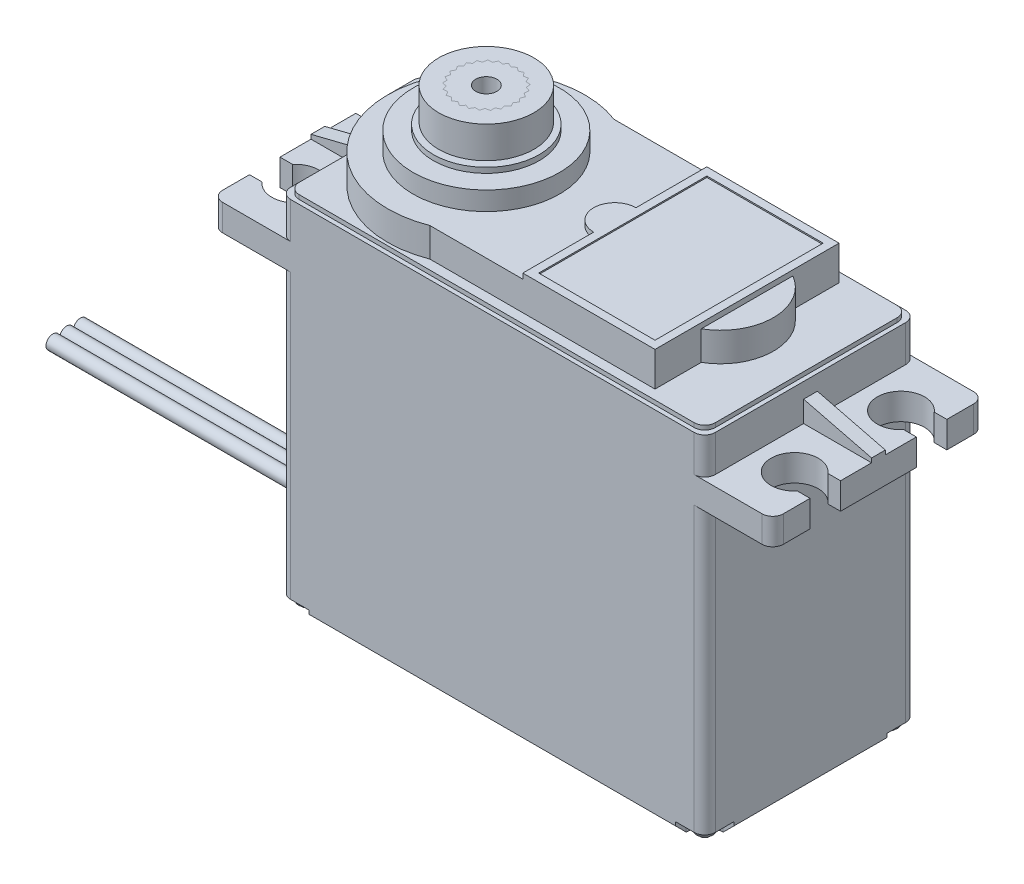
SolidWorks part; units mm, degrees
other "Camera1"
ref_plane "Front Plane" through (0, 0, 0) normal (0, 0, 1) x (1, 0, 0)
ref_plane "Top Plane" through (0, 0, 0) normal (0, 1, 0) x (1, 0, 0)
ref_plane "Right Plane" through (0, 0, 0) normal (1, 0, 0) x (0, 0, -1)
sketch "Sketch1" plane through (0, 0, 0) normal (0, 1, 0) x (1, 0, 0)
  line L1 (20.075, -10) -> (-20.075, -10)
  line L2 (20.075, -10) -> (20.075, 10)
  line L3 (20.075, 10) -> (-20.075, 10)
  line L4 (-20.075, -10) -> (-20.075, 10)
  line L5 (20.075, -10) -> (-20.075, 10) construction
  line L6 (20.075, 10) -> (-20.075, -10) construction
  point P0 (0, 0)
  dimension "D1" = 20
  dimension "D2" = 40.15
extrude "Boss-Extrude1" add sketch "Sketch1" along normal blind 34.5
sketch "Sketch2" plane through (0, 34.5, 0) normal (0, 1, 0) x (1, 0, 0)
  line L0 (-20.075, 0) -> (20.075, 0) construction
  line L1 (-20.075, 10) -> (-20.075, -10) construction
  line L2 (20.075, -10) -> (20.075, 10) construction
  line L3 (14.075, -4.3301) -> (14.075, -8.7)
  line L4 (-7.2047, 8.7) -> (14.075, 8.7)
  line L6 (-7.2047, -8.7) -> (14.075, -8.7)
  line L7 (14.075, 8.7) -> (14.075, 4.3301)
  arc A0 (-7.2047, 8.7) -> (-7.2047, -8.7) centre (-10.575, 0) ccw
  arc A1 (14.075, -4.3301) -> (14.075, 4.3301) centre (11.575, 0) ccw
  dimension "D2" = 18.66
  dimension "D5" = 10
  dimension "D1" = 9.5
  dimension "D3" = 17.4
  dimension "D4" = 6
  dimension "D6" = 8.5
sketch "Sketch3" plane through (0, 34.5, 0) normal (0, 1, 0) x (1, 0, 0)
  line L8 (-19.675, 9.6) -> (-19.675, -9.6)
  line L9 (-19.675, -9.6) -> (19.675, -9.6)
  line L10 (19.675, -9.6) -> (19.675, 9.6)
  line L11 (19.675, 9.6) -> (-19.675, 9.6)
  line L12 (-19.675, 9.6) -> (-19.675, -9.6)
  line L13 (-19.675, -9.6) -> (19.675, -9.6)
  line L14 (19.675, -9.6) -> (19.675, 9.6)
  line L15 (19.675, 9.6) -> (-19.675, 9.6)
  line L16 (-20.075, 10) -> (-20.075, -10)
  line L17 (-20.075, -10) -> (20.075, -10)
  line L18 (20.075, -10) -> (20.075, 10)
  line L19 (20.075, 10) -> (-20.075, 10)
  line L20 (-20.075, 10) -> (-20.075, -10)
  line L21 (-20.075, -10) -> (20.075, -10)
  line L22 (20.075, -10) -> (20.075, 10)
  line L23 (20.075, 10) -> (-20.075, 10)
  dimension "D1" = 0.4
  dimension "D2" = 0
extrude "Cut-Extrude1" cut sketch "Sketch3" against normal blind 0.4
extrude "Boss-Extrude2" add sketch "Sketch2" along normal mid plane 5.5
sketch "Sketch4" plane through (0, 37.25, 0) normal (0, 1, 0) x (1, 0, 0)
  circle A0 centre (-10.575, 0) radius 6.925
  dimension "D1" = 13.85
extrude "Boss-Extrude3" add sketch "Sketch4" along normal blind 1.77
sketch "Sketch5" plane through (0, 39.02, 0) normal (0, 1, 0) x (1, 0, 0)
  circle A0 centre (-10.575, 0) radius 5
  dimension "D1" = 10
extrude "Boss-Extrude4" add sketch "Sketch5" along normal blind 0.5
sketch "Sketch6" plane through (0, 37.25, 0) normal (0, 1, 0) x (1, 0, 0)
  line L0 (-7.2047, -8.7) -> (14.075, -8.7) construction
  line L1 (14.075, 8.7) -> (1.575, 8.7)
  line L2 (14.075, 8.7) -> (14.075, -8.7)
  line L3 (14.075, -8.7) -> (1.575, -8.7)
  line L4 (1.575, 8.7) -> (1.575, 2)
  line L5 (2.325, 7.95) -> (2.325, -7.95)
  line L6 (13.325, -7.95) -> (2.325, -7.95)
  line L7 (13.325, 7.95) -> (13.325, -7.95)
  line L8 (13.325, 7.95) -> (2.325, 7.95)
  line L9 (14.075, 0) -> (0, 0) construction
  line L10 (1.575, -2) -> (1.575, -8.7)
  line L11 (1.575, 8.7) -> (1.575, -8.7) construction
  line L12 (14.075, -8.7) -> (14.075, -4.3301) construction
  arc A0 (1.575, 2) -> (1.575, -2) centre (1.575, 0) ccw
  dimension "D3" = 4
  dimension "D2" = 12.5
  dimension "D1" = 0.75
extrude "Boss-Extrude5" add sketch "Sketch6" along normal blind 0.5
sketch "Sketch7" plane through (0, 37.25, 0) normal (0, 1, 0) x (1, 0, 0)
  line L4 (13.325, 7.95) -> (2.325, 7.95)
  line L5 (2.325, 7.95) -> (2.325, -7.95)
  line L6 (2.325, -7.95) -> (13.325, -7.95)
  line L7 (13.325, -7.95) -> (13.325, 7.95)
  line L8 (13.325, 7.95) -> (2.325, 7.95)
  line L9 (2.325, 7.95) -> (2.325, -7.95)
  line L10 (2.325, -7.95) -> (13.325, -7.95)
  line L11 (13.325, -7.95) -> (13.325, 7.95)
  dimension "D1" = 0
extrude "Boss-Extrude6" add sketch "Sketch7" along normal offset from surface (0.375 mm away) 0.125 up to face at (5.4083, 37.75, 0)
fillet "Fillet1" radius 1 8 edges at (19.675, 34.3, -9.6) (-19.675, 34.3, -9.6) (-19.675, 34.3, 9.6) (19.675, 34.3, 9.6) (20.075, 17.05, -10) (20.075, 17.05, 10) (-20.075, 17.05, -10) (-20.075, 17.05, 10)
sketch "Sketch10" plane through (0, 0, 0) normal (0, 1, 0) x (1, 0, 0)
  line L0 (-19.075, 10) -> (-25.5, 10)
  line L1 (-19.075, -10) -> (-25.5, -10)
  line L2 (-26.5, -9) -> (-26.5, -6.465)
  line L3 (19.075, 10) -> (25.5, 10)
  line L4 (26.5, 9) -> (26.5, 6.465)
  line L5 (25.5, -10) -> (19.075, -10)
  line L6 (23.6, 10) -> (23.6, -10) construction
  line L7 (-23.6, 10) -> (-23.6, -10) construction
  line L8 (-26.5, 0) -> (26.5, 0) construction
  line L9 (0, 10) -> (0, -10) construction
  line L10 (19.075, 10) -> (-19.075, 10) construction
  line L11 (-19.075, -10) -> (19.075, -10) construction
  line L12 (-23.6, 5.025) -> (23.6, 5.025) construction
  line L13 (23.6, -5.025) -> (-23.6, -5.025) construction
  line L14 (-26.5, 6.465) -> (-26.5, 9)
  line L15 (-26.5, 6.465) -> (-25.3093, 6.465)
  line L16 (-26.5, -3.585) -> (-26.5, 3.585)
  line L17 (-26.5, 3.585) -> (-25.3093, 3.585)
  line L18 (26.5, 3.585) -> (26.5, -3.585)
  line L19 (-26.5, -3.585) -> (-25.3093, -3.585)
  line L20 (26.5, -6.465) -> (26.5, -9)
  line L21 (-26.5, -6.465) -> (-25.3093, -6.465)
  line L22 (19.075, 10) -> (19.075, -10)
  line L23 (26.5, 6.465) -> (25.3093, 6.465)
  line L24 (-19.075, 10) -> (-19.075, -10)
  line L25 (26.5, 3.585) -> (25.3093, 3.585)
  line L27 (26.5, -3.585) -> (25.3093, -3.585)
  line L29 (26.5, -6.465) -> (25.3093, -6.465)
  arc A0 (-25.3093, 3.585) -> (-25.3093, 6.465) centre (-23.6, 5.025) ccw
  arc A1 (-25.3093, -6.465) -> (-25.3093, -3.585) centre (-23.6, -5.025) ccw
  arc A2 (25.3093, 6.465) -> (25.3093, 3.585) centre (23.6, 5.025) ccw
  arc A3 (25.3093, -3.585) -> (25.3093, -6.465) centre (23.6, -5.025) ccw
  arc A4 (-25.5, -10) -> (-26.5, -9) centre (-25.5, -9) cw
  arc A5 (-25.5, 10) -> (-26.5, 9) centre (-25.5, 9) ccw
  arc A6 (26.5, -9) -> (25.5, -10) centre (25.5, -9) cw
  arc A7 (25.5, 10) -> (26.5, 9) centre (25.5, 9) cw
  dimension "D1" = 4.47
  dimension "D5" = 1
  dimension "D2" = 10.05
  dimension "D3" = 47.2
  dimension "D4" = 53
  dimension "D6" = 2.88
  dimension "D7" = 2.88
  dimension "D8" = 2.88
  dimension "D9" = 2.88
extrude "Boss-Extrude7" add sketch "Sketch10" along normal blind 2.5 from offset 28.15
sketch "Sketch11" plane through (0, 0, 0) normal (0, 0, 1) x (1, 0, 0)
  line L0 (-20.075, 32.65) -> (-26.5, 31.0484)
  line L1 (-20.075, 30.65) -> (-20.075, 34.1) construction
  line L2 (-20.075, 32.65) -> (-20.075, 30.65)
  line L3 (-20.075, 30.65) -> (-26.5, 30.65)
  line L4 (20.075, 32.65) -> (26.5, 31.0484)
  line L5 (20.075, 34.1) -> (20.075, 30.65) construction
  line L6 (20.075, 32.65) -> (20.075, 30.65)
  line L7 (20.075, 30.65) -> (26.5, 30.65)
  line L8 (-26.5, 31.0484) -> (-26.5, 30.65)
  line L9 (26.5, 31.0484) -> (26.5, 30.65)
  dimension "D1" = 2
  dimension "D2" = 2
  dimension "D3" = 0.3984
extrude "Boss-Extrude8" add sketch "Sketch11" along normal mid plane 1.3
sketch "Sketch12" plane through (0, 0, 0) normal (0, -1, 0) x (1, 0, 0)
  line L0 (19.7821, 9.7071) -> (19.075, 9) construction
  line L2 (17.325, 9) -> (17.325, 10)
  line L4 (-19.075, 10) -> (19.075, 10) construction
  line L5 (19.075, 7.25) -> (20.075, 7.25)
  line L6 (20.075, -9) -> (20.075, 9) construction
  line L7 (17.325, 10) -> (19.075, 10)
  line L8 (20.075, 9) -> (20.075, 7.25)
  arc A1 (17.325, 9) -> (19.075, 7.25) centre (19.075, 9) ccw
  arc A2 (20.075, 9) -> (19.075, 10) centre (19.075, 9) ccw construction
  arc A3 (20.075, 9) -> (19.075, 10) centre (19.075, 9) ccw construction
  arc A4 (20.075, 9) -> (19.075, 10) centre (19.075, 9) ccw
  point P0 (19.075, 9)
  dimension "D1" = 3.5
extrude "Cut-Extrude2" cut sketch "Sketch12" against normal blind 1.35
mirror "Mirror1" about plane through (0, 0, 0) normal (0, 0, 1) of "Cut-Extrude2"
mirror "Mirror2" about plane through (0, 0, 0) normal (1, 0, 0) of "Mirror1"
chamfer "Chamfer1" distance 1 angle 45 4 edges at (20.075, 0, 0) (0, 0, -10) (-20.075, 0, 0) (0, 0, 10)
sketch "Sketch13" plane through (0, 39.52, 0) normal (0, 1, 0) x (1, 0, 0)
  line L0 (-10.575, 2.935) -> (-10.9115, 2.6638)
  line L1 (-10.575, 2.935) -> (-10.2385, 2.6638)
  line L2 (-10.575, 2.935) -> (-10.575, 0) construction
  line L3 (-9.8451, 2.8428) -> (-9.5866, 2.4964)
  line L4 (-9.8451, 2.8428) -> (-10.2385, 2.6638)
  line L5 (-9.1611, 2.572) -> (-8.9968, 2.1722)
  line L6 (-9.1611, 2.572) -> (-9.5866, 2.4964)
  line L7 (-8.5659, 2.1395) -> (-8.5062, 1.7115)
  line L8 (-8.5659, 2.1395) -> (-8.9968, 2.1722)
  line L9 (-8.0969, 1.5727) -> (-8.1455, 1.1432)
  line L10 (-8.0969, 1.5727) -> (-8.5062, 1.7115)
  line L11 (-7.7836, 0.907) -> (-7.9376, 0.5031)
  line L12 (-7.7836, 0.907) -> (-8.1455, 1.1432)
  line L13 (-7.6458, 0.1843) -> (-7.8953, -0.1686)
  line L14 (-7.6458, 0.1843) -> (-7.9376, 0.5031)
  line L15 (-7.692, -0.55) -> (-8.0214, -0.8297)
  line L16 (-7.692, -0.55) -> (-7.8953, -0.1686)
  line L17 (-7.9193, -1.2497) -> (-8.308, -1.4387)
  line L18 (-7.9193, -1.2497) -> (-8.0214, -0.8297)
  line L19 (-8.3135, -1.8708) -> (-8.737, -1.9573)
  line L20 (-8.3135, -1.8708) -> (-8.308, -1.4387)
  line L21 (-8.8499, -2.3745) -> (-9.2815, -2.3529)
  line L22 (-8.8499, -2.3745) -> (-8.737, -1.9573)
  line L23 (-9.4946, -2.7289) -> (-9.9073, -2.6006)
  line L24 (-9.4946, -2.7289) -> (-9.2815, -2.3529)
  line L25 (-10.2071, -2.9119) -> (-10.575, -2.685)
  line L26 (-10.2071, -2.9119) -> (-9.9073, -2.6006)
  line L27 (-10.9429, -2.9119) -> (-11.2427, -2.6006)
  line L28 (-10.9429, -2.9119) -> (-10.575, -2.685)
  line L29 (-11.6554, -2.7289) -> (-11.8685, -2.3529)
  line L30 (-11.6554, -2.7289) -> (-11.2427, -2.6006)
  line L31 (-12.3001, -2.3745) -> (-12.413, -1.9573)
  line L32 (-12.3001, -2.3745) -> (-11.8685, -2.3529)
  line L33 (-12.8365, -1.8708) -> (-12.842, -1.4387)
  line L34 (-12.8365, -1.8708) -> (-12.413, -1.9573)
  line L35 (-13.2307, -1.2497) -> (-13.1286, -0.8297)
  line L36 (-13.2307, -1.2497) -> (-12.842, -1.4387)
  line L37 (-13.458, -0.55) -> (-13.2547, -0.1686)
  line L38 (-13.458, -0.55) -> (-13.1286, -0.8297)
  line L39 (-13.5042, 0.1843) -> (-13.2124, 0.5031)
  line L40 (-13.5042, 0.1843) -> (-13.2547, -0.1686)
  line L41 (-13.3664, 0.907) -> (-13.0045, 1.1432)
  line L42 (-13.3664, 0.907) -> (-13.2124, 0.5031)
  line L43 (-13.0531, 1.5727) -> (-12.6438, 1.7115)
  line L44 (-13.0531, 1.5727) -> (-13.0045, 1.1432)
  line L45 (-12.5841, 2.1395) -> (-12.1532, 2.1722)
  line L46 (-12.5841, 2.1395) -> (-12.6438, 1.7115)
  line L47 (-11.9889, 2.572) -> (-11.5634, 2.4964)
  line L48 (-11.9889, 2.572) -> (-12.1532, 2.1722)
  line L49 (-11.3049, 2.8428) -> (-10.9115, 2.6638)
  line L50 (-11.3049, 2.8428) -> (-11.5634, 2.4964)
  circle A0 centre (-10.575, 0) radius 2.935 construction
  circle A1 centre (-10.575, 0) radius 2.685 construction
  point P83 (-10.575, 0)
  dimension "D1" = 5.87
  dimension "D2" = 0.25
  dimension "D4" = 25
extrude "Boss-Extrude9" add sketch "Sketch13" along normal blind 3.18
sketch "Sketch14" plane through (0, 42.7, 0) normal (0, 1, 0) x (1, 0, 0)
  circle A0 centre (-10.575, 0) radius 1
  point P0 (-10.575, 0)
  dimension "D1" = 2
sketch "Sketch15" plane through (-20.075, 0, 0) normal (-1, 0, 0) x (0, 0, 1)
  line L0 (0, 0) -> (0, 10.6216) construction
  line L1 (-7.25, 1) -> (7.25, 1) construction
  line L2 (-2.9, 1) -> (2.9, 1)
  line L3 (-2.9, 1) -> (-2.9, 4)
  line L4 (-2.9, 4) -> (2.9, 4)
  line L5 (2.9, 1) -> (2.9, 4)
  dimension "D1" = 3
  dimension "D2" = 5.8
ref_plane "Plane2" through (-25.075, 0, 0) normal (-1, 0, 0) x (0, 0, 1)
sketch "Sketch16" plane through (-25.075, 0, 0) normal (-1, 0, 0) x (0, 0, 1)
  line L14 (-2.15, 1.75) -> (2.15, 1.75)
  line L15 (2.15, 1.75) -> (2.15, 3.25)
  line L16 (-2.15, 3.25) -> (-2.15, 1.75)
  line L17 (2.15, 3.25) -> (-2.15, 3.25)
  line L18 (-2.15, 1.75) -> (2.15, 1.75)
  line L19 (2.15, 1.75) -> (2.15, 3.25)
  line L20 (-2.15, 3.25) -> (-2.15, 1.75)
  line L21 (2.15, 3.25) -> (-2.15, 3.25)
  dimension "D1" = 0.75
loft "Loft1" add profiles "Sketch16", "Sketch15" connector at (-25.075, 3.25, 2.15) connector at (-20.075, 4, 2.9)
sketch "Sketch17" plane through (-25.075, 0, 0) normal (-1, 0, 0) x (0, 0, 1)
  line L0 (-2.15, 2.5) -> (2.15, 2.5) construction
  line L1 (-2.15, 3.25) -> (-2.15, 1.75) construction
  line L2 (2.15, 1.75) -> (2.15, 3.25) construction
  line L3 (0.6379, 2.625) -> (0.6621, 2.625)
  line L4 (-0.6621, 2.375) -> (-0.6379, 2.375)
  line L6 (0.6379, 2.375) -> (0.6621, 2.375)
  line L7 (-0.6621, 2.625) -> (-0.6379, 2.625)
  arc A0 (-0.6379, 2.375) -> (0.6379, 2.375) centre (0, 2.5) ccw
  arc A1 (-0.6621, 2.625) -> (-0.6621, 2.375) centre (-1.3, 2.5) ccw
  arc A2 (0.6621, 2.375) -> (0.6621, 2.625) centre (1.3, 2.5) ccw
  arc A3 (0.6379, 2.625) -> (-0.6379, 2.625) centre (0, 2.5) ccw
  dimension "D1" = 1.3
  dimension "D2" = 0.25
extrude "Boss-Extrude11" add sketch "Sketch17" along normal blind 25.18
extrude "Cut-Extrude4" cut sketch "Sketch14" against normal up to surface (3.18 mm away) up to face at (-10.575, 39.52, 5)
sketch "Sketch18" plane through (0, 1.35, 0) normal (0, -1, 0) x (1, 0, 0)
  line L0 (19.7821, 9.7071) -> (17.8376, 7.7626) construction
  arc A0 (20.075, 9) -> (19.075, 10) centre (19.075, 9) ccw construction
  arc A1 (17.325, 9) -> (19.075, 7.25) centre (19.075, 9) ccw construction
  point P8 (18.8098, 8.7348)
ref_plane "Plane3" through (18.8098, 0, 0) normal (1, 0, 0) x (0, 0, -1)
sketch "Sketch19" plane through (18.8098, 0, 0) normal (1, 0, 0) x (0, 0, -1)
  line L0 (-9.7071, 1.35) -> (-7.7626, 1.35) construction
  line L1 (-9.7071, 1.35) -> (-7.7626, 1.35)
  line L2 (-8.7348, 1.35) -> (-8.7348, 0.3777) construction
  arc A0 (-9.7071, 1.35) -> (-7.7626, 1.35) centre (-8.7348, 1.35) ccw
  point P0 (-8.7348, 1.35)
revolve "Revolve1" add sketch "Sketch19" angle 360 about L2 region at (18.8098, 0.9374, 9.1475)
sketch "Sketch20" plane through (0, 1.35, 0) normal (0, -1, 0) x (1, 0, 0)
  line L0 (19.7821, 9.7071) -> (17.8376, 7.7626) construction
  line L1 (19.0598, 7.9848) -> (18.5598, 7.9848)
  line L2 (19.0598, 7.9848) -> (19.0598, 9.4848)
  line L3 (19.0598, 9.4848) -> (18.5598, 9.4848)
  line L4 (18.5598, 7.9848) -> (18.5598, 9.4848)
  line L5 (19.0598, 7.9848) -> (18.5598, 9.4848) construction
  line L6 (19.0598, 9.4848) -> (18.5598, 7.9848) construction
  line L8 (19.5598, 8.9848) -> (18.0598, 8.9848)
  line L9 (19.5598, 8.9848) -> (19.5598, 8.4848)
  line L10 (19.5598, 8.4848) -> (18.0598, 8.4848)
  line L11 (18.0598, 8.9848) -> (18.0598, 8.4848)
  line L12 (19.5598, 8.9848) -> (18.0598, 8.4848) construction
  line L13 (19.5598, 8.4848) -> (18.0598, 8.9848) construction
  point P0 (18.8098, 8.7348)
  point P7 (18.8098, 8.7348)
  dimension "D1" = 0.5
  dimension "D2" = 1.5
extrude "Cut-Extrude5" cut sketch "Sketch20" against normal blind 0.5 from offset 1 contours L8 L2 L3 L4 | L10 L9 L8 L2 | L10 L2 L8 L4 | L2 L10 L4 L1 | L8 L11 L10 L4 region at (18.8098, 1.35, 8.2348) region at (18.8098, 1.35, 8.7348) region at (19.3098, 1.35, 8.7348) region at (18.3098, 1.35, 8.7348) region at (18.8098, 1.35, 9.2348)
mirror "Mirror3" about plane through (0, 0, 0) normal (0, 0, 1) of "Cut-Extrude5", "Revolve1"
mirror "Mirror4" about plane through (0, 0, 0) normal (1, 0, 0) of "Mirror3"
sketch "Sketch22"
sketch "Sketch23" plane through (0, 42.7, 0) normal (0, 1, 0) x (1, 0, 0)
  line L50 (-10.2385, 2.6638) -> (-10.575, 2.935)
  line L51 (-10.575, 2.935) -> (-10.9115, 2.6638)
  line L52 (-10.9115, 2.6638) -> (-11.3049, 2.8428)
  line L53 (-11.3049, 2.8428) -> (-11.5634, 2.4964)
  line L54 (-11.5634, 2.4964) -> (-11.9889, 2.572)
  line L55 (-11.9889, 2.572) -> (-12.1532, 2.1722)
  line L56 (-12.1532, 2.1722) -> (-12.5841, 2.1395)
  line L57 (-12.5841, 2.1395) -> (-12.6438, 1.7115)
  line L58 (-12.6438, 1.7115) -> (-13.0531, 1.5727)
  line L59 (-13.0531, 1.5727) -> (-13.0045, 1.1432)
  line L60 (-13.0045, 1.1432) -> (-13.3664, 0.907)
  line L61 (-13.3664, 0.907) -> (-13.2124, 0.5031)
  line L62 (-13.2124, 0.5031) -> (-13.5042, 0.1843)
  line L63 (-13.5042, 0.1843) -> (-13.2547, -0.1686)
  line L64 (-13.2547, -0.1686) -> (-13.458, -0.55)
  line L65 (-13.458, -0.55) -> (-13.1286, -0.8297)
  line L66 (-13.1286, -0.8297) -> (-13.2307, -1.2497)
  line L67 (-13.2307, -1.2497) -> (-12.842, -1.4387)
  line L68 (-12.842, -1.4387) -> (-12.8365, -1.8708)
  line L69 (-12.8365, -1.8708) -> (-12.413, -1.9573)
  line L70 (-12.413, -1.9573) -> (-12.3001, -2.3745)
  line L71 (-12.3001, -2.3745) -> (-11.8685, -2.3529)
  line L72 (-11.8685, -2.3529) -> (-11.6554, -2.7289)
  line L73 (-11.6554, -2.7289) -> (-11.2427, -2.6006)
  line L74 (-11.2427, -2.6006) -> (-10.9429, -2.9119)
  line L75 (-10.9429, -2.9119) -> (-10.575, -2.685)
  line L76 (-10.575, -2.685) -> (-10.2071, -2.9119)
  line L77 (-10.2071, -2.9119) -> (-9.9073, -2.6006)
  line L78 (-9.9073, -2.6006) -> (-9.4946, -2.7289)
  line L79 (-9.4946, -2.7289) -> (-9.2815, -2.3529)
  line L80 (-9.2815, -2.3529) -> (-8.8499, -2.3745)
  line L81 (-8.8499, -2.3745) -> (-8.737, -1.9573)
  line L82 (-8.737, -1.9573) -> (-8.3135, -1.8708)
  line L83 (-8.3135, -1.8708) -> (-8.308, -1.4387)
  line L84 (-8.308, -1.4387) -> (-7.9193, -1.2497)
  line L85 (-7.9193, -1.2497) -> (-8.0214, -0.8297)
  line L86 (-8.0214, -0.8297) -> (-7.692, -0.55)
  line L87 (-7.692, -0.55) -> (-7.8953, -0.1686)
  line L88 (-7.8953, -0.1686) -> (-7.6458, 0.1843)
  line L89 (-7.6458, 0.1843) -> (-7.9376, 0.5031)
  line L90 (-7.9376, 0.5031) -> (-7.7836, 0.907)
  line L91 (-7.7836, 0.907) -> (-8.1455, 1.1432)
  line L92 (-8.1455, 1.1432) -> (-8.0969, 1.5727)
  line L93 (-8.0969, 1.5727) -> (-8.5062, 1.7115)
  line L94 (-8.5062, 1.7115) -> (-8.5659, 2.1395)
  line L95 (-8.5659, 2.1395) -> (-8.9968, 2.1722)
  line L96 (-8.9968, 2.1722) -> (-9.1611, 2.572)
  line L97 (-9.1611, 2.572) -> (-9.5866, 2.4964)
  line L98 (-9.5866, 2.4964) -> (-9.8451, 2.8428)
  line L99 (-9.8451, 2.8428) -> (-10.2385, 2.6638)
  line L100 (-10.2385, 2.6638) -> (-10.575, 2.935)
  line L101 (-10.575, 2.935) -> (-10.9115, 2.6638)
  line L102 (-10.9115, 2.6638) -> (-11.3049, 2.8428)
  line L103 (-11.3049, 2.8428) -> (-11.5634, 2.4964)
  line L104 (-11.5634, 2.4964) -> (-11.9889, 2.572)
  line L105 (-11.9889, 2.572) -> (-12.1532, 2.1722)
  line L106 (-12.1532, 2.1722) -> (-12.5841, 2.1395)
  line L107 (-12.5841, 2.1395) -> (-12.6438, 1.7115)
  line L108 (-12.6438, 1.7115) -> (-13.0531, 1.5727)
  line L109 (-13.0531, 1.5727) -> (-13.0045, 1.1432)
  line L110 (-13.0045, 1.1432) -> (-13.3664, 0.907)
  line L111 (-13.3664, 0.907) -> (-13.2124, 0.5031)
  line L112 (-13.2124, 0.5031) -> (-13.5042, 0.1843)
  line L113 (-13.5042, 0.1843) -> (-13.2547, -0.1686)
  line L114 (-13.2547, -0.1686) -> (-13.458, -0.55)
  line L115 (-13.458, -0.55) -> (-13.1286, -0.8297)
  line L116 (-13.1286, -0.8297) -> (-13.2307, -1.2497)
  line L117 (-13.2307, -1.2497) -> (-12.842, -1.4387)
  line L118 (-12.842, -1.4387) -> (-12.8365, -1.8708)
  line L119 (-12.8365, -1.8708) -> (-12.413, -1.9573)
  line L120 (-12.413, -1.9573) -> (-12.3001, -2.3745)
  line L121 (-12.3001, -2.3745) -> (-11.8685, -2.3529)
  line L122 (-11.8685, -2.3529) -> (-11.6554, -2.7289)
  line L123 (-11.6554, -2.7289) -> (-11.2427, -2.6006)
  line L124 (-11.2427, -2.6006) -> (-10.9429, -2.9119)
  line L125 (-10.9429, -2.9119) -> (-10.575, -2.685)
  line L126 (-10.575, -2.685) -> (-10.2071, -2.9119)
  line L127 (-10.2071, -2.9119) -> (-9.9073, -2.6006)
  line L128 (-9.9073, -2.6006) -> (-9.4946, -2.7289)
  line L129 (-9.4946, -2.7289) -> (-9.2815, -2.3529)
  line L130 (-9.2815, -2.3529) -> (-8.8499, -2.3745)
  line L131 (-8.8499, -2.3745) -> (-8.737, -1.9573)
  line L132 (-8.737, -1.9573) -> (-8.3135, -1.8708)
  line L133 (-8.3135, -1.8708) -> (-8.308, -1.4387)
  line L134 (-8.308, -1.4387) -> (-7.9193, -1.2497)
  line L135 (-7.9193, -1.2497) -> (-8.0214, -0.8297)
  line L136 (-8.0214, -0.8297) -> (-7.692, -0.55)
  line L137 (-7.692, -0.55) -> (-7.8953, -0.1686)
  line L138 (-7.8953, -0.1686) -> (-7.6458, 0.1843)
  line L139 (-7.6458, 0.1843) -> (-7.9376, 0.5031)
  line L140 (-7.9376, 0.5031) -> (-7.7836, 0.907)
  line L141 (-7.7836, 0.907) -> (-8.1455, 1.1432)
  line L142 (-8.1455, 1.1432) -> (-8.0969, 1.5727)
  line L143 (-8.0969, 1.5727) -> (-8.5062, 1.7115)
  line L144 (-8.5062, 1.7115) -> (-8.5659, 2.1395)
  line L145 (-8.5659, 2.1395) -> (-8.9968, 2.1722)
  line L146 (-8.9968, 2.1722) -> (-9.1611, 2.572)
  line L147 (-9.1611, 2.572) -> (-9.5866, 2.4964)
  line L148 (-9.5866, 2.4964) -> (-9.8451, 2.8428)
  line L149 (-9.8451, 2.8428) -> (-10.2385, 2.6638)
  circle A0 centre (-10.575, 0) radius 4.5
  dimension "D2" = 9
  dimension "D1" = 0
extrude "Boss-Extrude12" add sketch "Sketch23" against normal blind 3 separate body
equation "\"W\"=0.525804"
